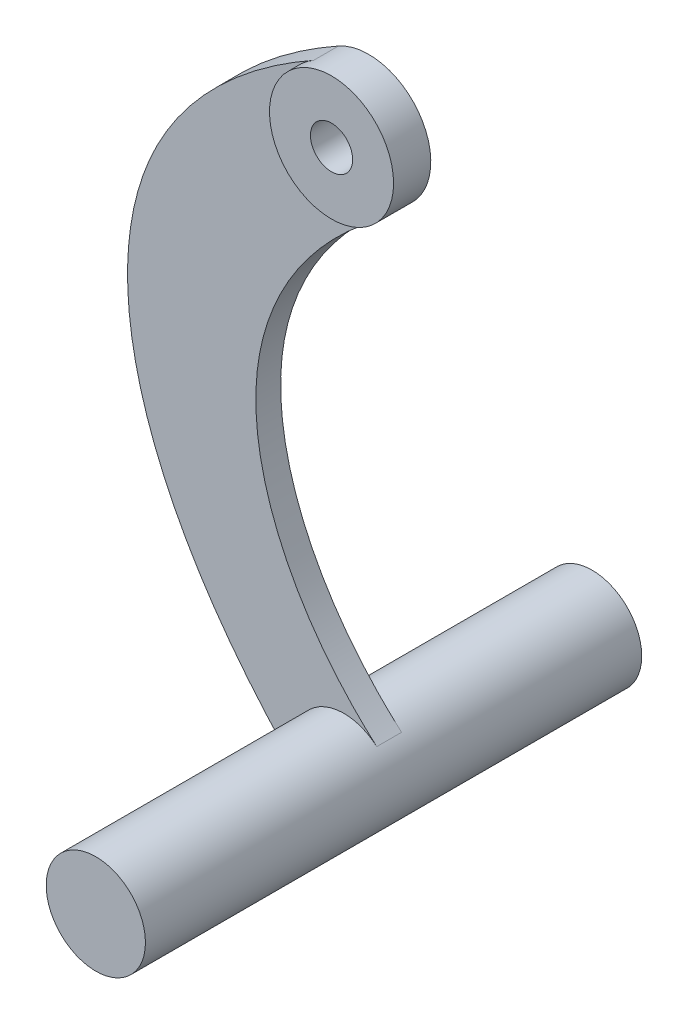
SolidWorks part; units mm, degrees
ref_plane "Спереди" through (0, 0, 0) normal (0, 0, 1) x (1, 0, 0)
ref_plane "Сверху" through (0, 0, 0) normal (0, 1, 0) x (1, 0, 0)
ref_plane "Справа" through (0, 0, 0) normal (1, 0, 0) x (0, 0, -1)
other "Configuration Table"
sketch "Sketch1" plane through (0, 0, 0) normal (0, 0, 1) x (1, 0, 0)
  circle A0 centre (0, 0) radius 4.25
  circle A1 centre (0, 0) radius 12.5
  dimension "D1" = 8.5
  dimension "D2" = 25
extrude "Boss-Extrude1" add sketch "Sketch1" along normal blind 2.5
sketch "Sketch2" plane through (0, 0, 0) normal (0, 0, -1) x (-1, 0, 0)
  arc A0 (-6.6111, -102.4971) -> (7.0028, -117.1387) centre (0, -110) ccw
  circle A1 centre (0, 0) radius 12.5 construction
  arc A2 (6.1064, 10.907) -> (-7.4068, -10.0692) centre (0, 0) ccw
  spline S0 degree 3 poles (-7.4068, -10.0692) (7.9799, -21.3875) (26.8557, -52.6463) (9.4398, -88.354) (-6.6111, -102.4971) knots 0 0 0 0 0.455822 1 1 1 1
  spline S1 degree 3 poles (6.1064, 10.907) (20.6217, 2.7804) (57.0301, -32.0145) (40.003, -84.7667) (7.0028, -117.1387) knots 0 0 0 0 0.302024 1 1 1 1
  dimension "D2" = 20
  dimension "D1" = 110
extrude "Boss-Extrude2" add sketch "Sketch2" along normal blind 5
sketch "Sketch3" plane through (0, 0, 0) normal (0, 0, 1) x (1, 0, 0)
  circle A0 centre (0, -110) radius 10
  dimension "D1" = 20
extrude "Boss-Extrude3" add sketch "Sketch3" along normal blind 50 and the other way blind 50
sketch "Sketch4" plane through (0, 0, 0) normal (0, 0, 1) x (1, 0, 0)
  circle A0 centre (0, 0) radius 4.25
  dimension "D1" = 8.5
extrude "Cut-Extrude1" cut sketch "Sketch4" against normal blind 40
